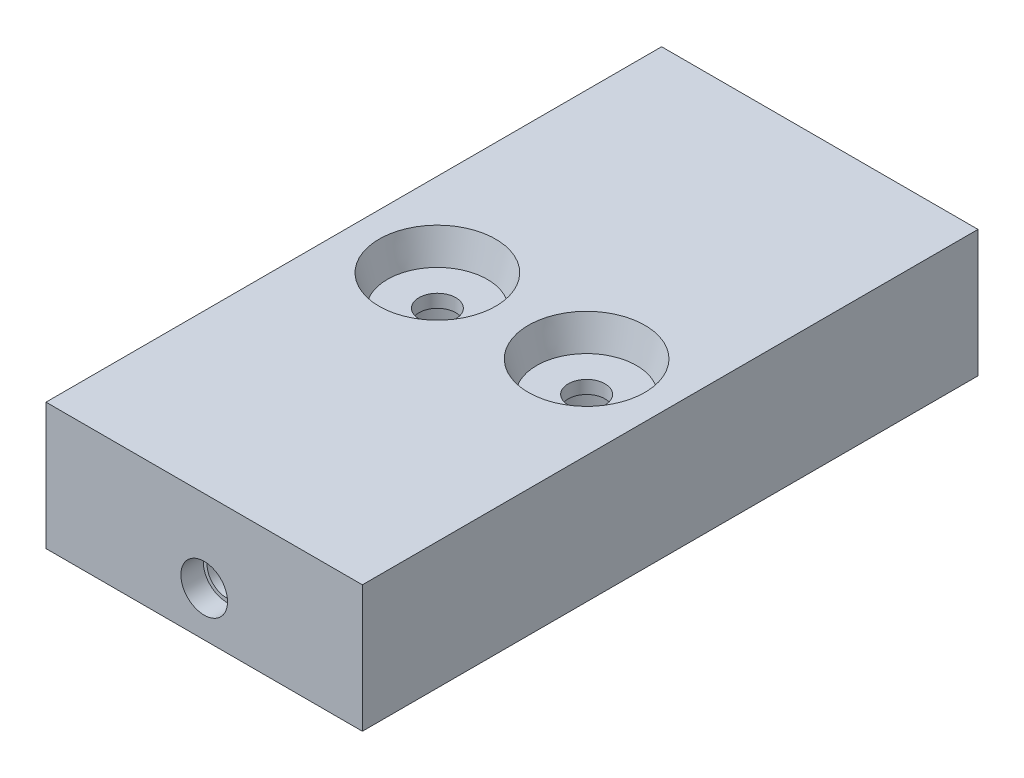
SolidWorks part; units mm, degrees
note: The reader was unsure of these and kept them because the rebuilt part matched: shared geometry of "Sketch1<3>", "Sketch1<4>".
material "ABS"
ref_plane "Front Plane" through (0, 0, 0) normal (0, 0, 1) x (1, 0, 0)
ref_plane "Top Plane" through (0, 0, 0) normal (0, 1, 0) x (1, 0, 0)
ref_plane "Right Plane" through (0, 0, 0) normal (1, 0, 0) x (0, 0, -1)
sketch "Sketch1" plane through (0, 0, 0) normal (0, 1, 0) x (1, 0, 0)
  line L0 (-20, 0) -> (20, 0) construction
  line L1 (0, -82.5) -> (0, 82.5) construction
  line L3 (-42.4, 82.5) -> (42.4, 82.5)
  line L4 (-42.4, 82.5) -> (-42.4, -82.5)
  line L5 (-42.4, -82.5) -> (42.4, -82.5)
  line L6 (42.4, 82.5) -> (42.4, -82.5)
  circle A0 centre (-20, 0) radius 4.925
  circle A1 centre (20, 0) radius 4.925
  circle A2 centre (-20, 0) radius 13.4
  circle A3 centre (20, 0) radius 13.4
  dimension "D1" = 9.85
  dimension "D3" = 26.8
  dimension "D4" = 9
  dimension "D2" = 40
  dimension "D5" = 165
extrude "Boss-Extrude1" add sketch "Sketch1" along normal mid plane 3.5 contours L6 L3 L4 L5 A2 A3 | A2 A0 | A3 A1
extrude "Boss-Extrude2" add sketch "Sketch1<3>" along normal blind 10 contours L6 L3 L4 L5 A2 A3
sketch "Sketch1<3>" plane through (0, 0, 0) normal (0, 1, 0) x (1, 0, 0) same geometry as "Sketch1"
extrude "Boss-Extrude3" add sketch "Sketch1<4>" against normal blind 24 contours L6 L3 L4 L5 A2 A3
sketch "Sketch1<4>" plane through (0, 0, 0) normal (0, 1, 0) x (1, 0, 0) same geometry as "Sketch1"
ref_plane "Plane1" through (0, -12, 0) normal (0, 1, 0) x (1, 0, 0)
sketch "Sketch3" plane through (0, -12, 0) normal (0, 1, 0) x (1, 0, 0)
  line L0 (0, -82.5) -> (0, 0) construction
  line L1 (-42.4, -82.5) -> (42.4, -82.5) construction
  line L2 (-6.25, -82.5) -> (-6.25, -76.5)
  line L3 (-6.25, -76.5) -> (-5.25, -76.5)
  line L4 (-5.25, -76.5) -> (-5.25, -61.5)
  line L5 (-5.25, -61.5) -> (-4.05, -61.5)
  line L6 (-4.05, -61.5) -> (-4.05, -47.5)
  line L7 (-4.05, -47.5) -> (0, -47.5)
  line L8 (-6.25, -82.5) -> (0, -82.5)
  line L9 (0, -82.5) -> (0, -47.5)
  dimension "D1" = 35
  dimension "D2" = 6
  dimension "D3" = 8.1
  dimension "D4" = 10.5
  dimension "D5" = 15
  dimension "D6" = 12.5
revolve "Cut-Revolve1" cut sketch "Sketch3" angle 360 about L0
mirror "Mirror1" about plane through (0, 0, 0) normal (0, 0, 1) of "Cut-Revolve1"
sketch "Sketch4" plane through (0, 0, 0) normal (0, 0, 1) x (1, 0, 0)
  line L0 (0, 0) -> (0, 18.0942) construction
  line L2 (0, 0) -> (-8.5015, 12.1414) construction
  line L3 (-8.5015, 12.1414) -> (0, 18.0942) construction
  dimension "D1" = 35
draft "Draft1" type of draft neutral plane draft angle 15 faces to draft 2 face at (-20, 1.75, 13.4) face at (20, 1.75, 13.4) neutral plane through (0, 1.75, 0) neutral plane normal (0, 1, 0) parameters "D1"=15
other "Graphic1" [suppressed]
other "Graphic (Closed) -1"
